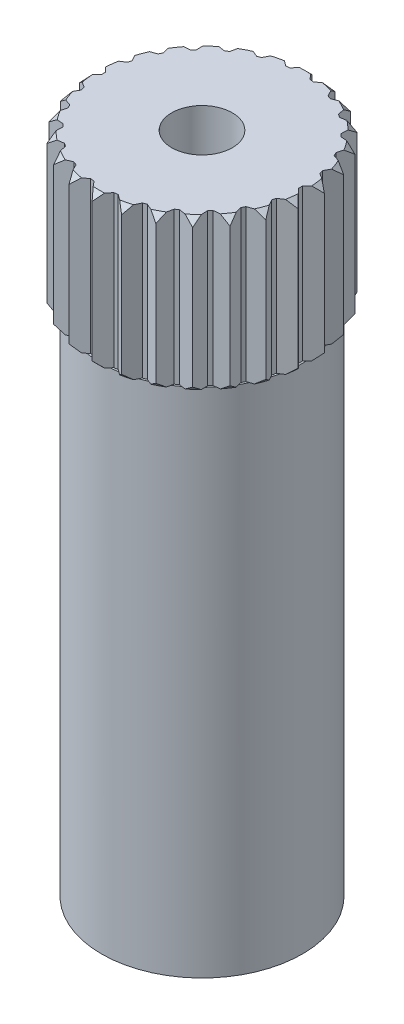
SolidWorks part; units mm, degrees
material "Brass"
ref_plane "Front Plane" through (0, 0, 0) normal (0, 0, 1) x (1, 0, 0)
ref_plane "Top Plane" through (0, 0, 0) normal (0, 1, 0) x (1, 0, 0)
ref_plane "Right Plane" through (0, 0, 0) normal (1, 0, 0) x (0, 0, -1)
sketch "Sketch12" plane through (0, 0, 0) normal (0, 1, 0) x (1, 0, 0)
  circle A0 centre (0, 0) radius 2.9
  dimension "D1" = 5.8
extrude "Boss-Extrude4" add sketch "Sketch12" along normal blind 13.5 separate body
sketch "Sketch13" plane through (0, 13.5, 0) normal (0, 1, 0) x (1, 0, 0)
  circle A2 centre (0, 0) radius 2.6
  circle A3 centre (0, 0) radius 2.9 construction
  dimension "D1" = 0.3
extrude "Boss-Extrude5" add sketch "Sketch13" along normal blind 4
sketch "Sketch14" plane through (0, 17.5, 0) normal (0, 1, 0) x (1, 0, 0)
  line L0 (0, 2.6) -> (0, 2.9) construction
  line L1 (0, 2.9) -> (-0.2629, 2.5867)
  line L2 (0, 2.9) -> (0.2629, 2.5867)
  line L3 (-0.2629, 2.5867) -> (0.2629, 2.5867) construction
  circle A0 centre (0, 0) radius 2.9 construction
  circle A1 centre (0, 0) radius 2.6
  arc A2 (0.2629, 2.5867) -> (-0.2629, 2.5867) centre (0, 0) ccw
  dimension "D2" = 80
  dimension "D3" = 0.5258
  dimension "D4" = 0.3
  dimension "D1" = 0
extrude "Boss-Extrude6" add sketch "Sketch14" against normal up to body separate body
pattern_circular "CirPattern1" count 26 over 360 about axis through (0, 17.5, 0) along (0, -1, 0) of "Boss-Extrude6"
sketch "Sketch15" plane through (0, 0, 0) normal (1, 0, 0) x (0, 0, -1)
  line L0 (2.9, 17.3232) -> (2.9, 17.5)
  line L1 (2.9, 13.5) -> (2.9, 17.5) construction
  line L2 (2.9, 17.5) -> (2.7232, 17.5)
  line L3 (2.1682, 17.5) -> (2.5678, 17.5) construction
  line L4 (2.7232, 17.5) -> (2.9, 17.3232)
  dimension "D1" = 45
  dimension "D2" = 0.25
revolve "Cut-Revolve1" cut sketch "Sketch15" angle 360 about axis through (0, 17.5, 0) along (0, -1, 0)
sketch "Sketch16" plane through (0, 17.5, 0) normal (0, 1, 0) x (1, 0, 0)
  circle A0 centre (0, 0) radius 0.8
  dimension "D1" = 1.6
extrude "Cut-Extrude1" cut sketch "Sketch16" against normal blind 4
ref_plane "Plane1" through (-0.3638, 13.5, -2.5744) normal (-0.9902, 0, 0.1399) x (0.1399, 0, 0.9902)
sketch "Sketch17" plane through (0, 0, 0) normal (0, 0, 1) x (1, 0, 0)
  line L0 (2.9, 0) -> (2.65, 0)
  line L1 (-2.9, 0) -> (2.9, 0) construction
  line L2 (2.65, 0) -> (2.65, 13.5)
  line L3 (2.65, 13.5) -> (2.9, 13.5)
  line L4 (2.9, 13.5) -> (2.9, 0)
  line L5 (0, 0) -> (2.65, 0) construction
  line L6 (2.7115, 13.5) -> (2.3254, 13.5) construction
  dimension "D1" = 0.25
  dimension "D2" = 2.65
  dimension "D3" = 2.9
revolve "Cut-Revolve2" cut sketch "Sketch17" angle 360 about axis through (0, 13.5, 0) along (0, -1, 0)
ref_plane "Plane2" through (0, 15.5, 0) normal (0, 1, 0) x (1, 0, 0)
mirror "Mirror1" about plane through (0, 15.5, 0) normal (0, 1, 0) of "Cut-Revolve1"
